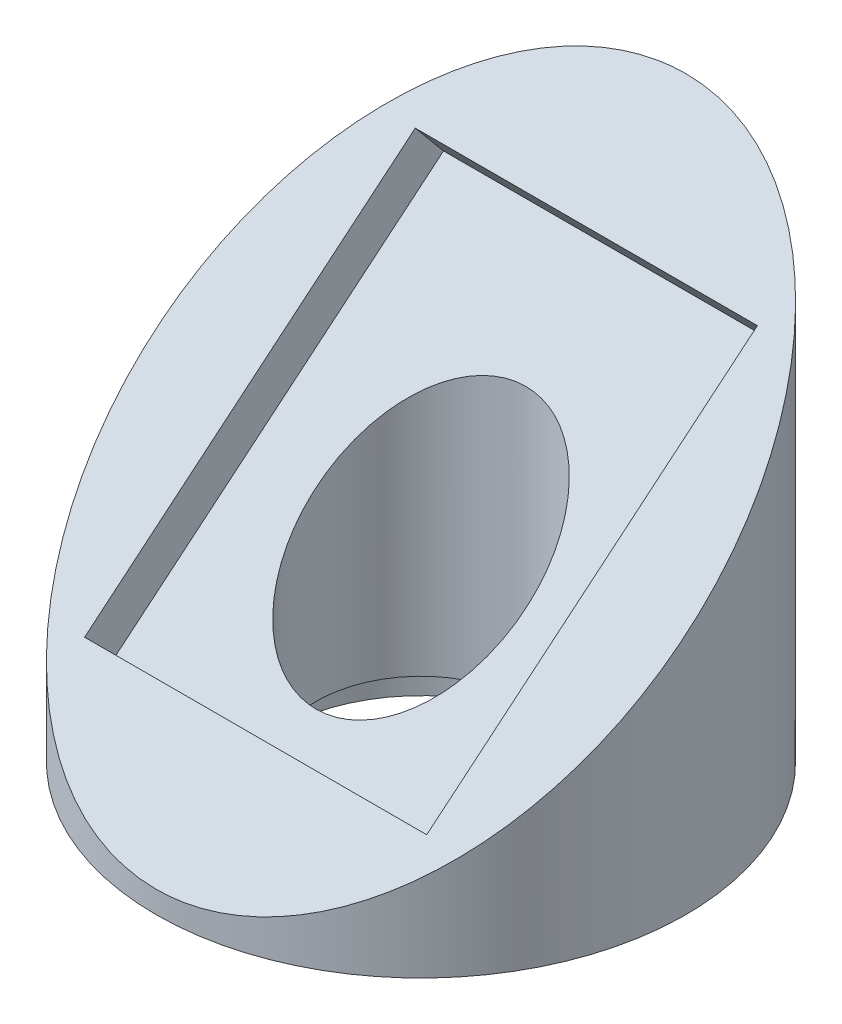
SolidWorks part; units mm, degrees
ref_plane "Front Plane" through (0, 0, 0) normal (0, 0, 1) x (1, 0, 0)
ref_plane "Top Plane" through (0, 0, 0) normal (0, 1, 0) x (1, 0, 0)
ref_plane "Right Plane" through (0, 0, 0) normal (1, 0, 0) x (0, 0, -1)
sketch "Sketch2" plane through (0, 0, 0) normal (0, 1, 0) x (1, 0, 0)
  circle A0 centre (0, 0) radius 4.75
  circle A1 centre (0, 0) radius 6.5
  circle A2 centre (0, 0) radius 12
  circle A3 centre (0, 0) radius 7.5
extrude "Boss-Extrude2" add sketch "Sketch2" against normal blind 1 contours A1 A0 | A3 A1 | A2 A3 region at (-6.3162, 0, 0) region at (-11.6606, 0, 0) region at (-7.2879, 0, 0)
extrude "Boss-Extrude3" add sketch "Sketch2<4>" against normal blind 3 contours A3 A1 region at (-7.2879, 0, 0)
sketch "Sketch2<4>" plane through (0, 0, 0) normal (0, 1, 0) x (1, 0, 0) same geometry as "Sketch2"
extrude "Boss-Extrude4" add sketch "Sketch2<5>" along normal blind 20 contours A0 | A2 region at (0, 0, 0)
sketch "Sketch2<5>" plane through (0, 0, 0) normal (0, 1, 0) x (1, 0, 0) same geometry as "Sketch2"
sketch "Sketch5" plane through (0, 0, 0) normal (1, 0, 0) x (0, 0, -1)
  line L0 (-12, -1) -> (-12, 0)
  line L1 (-12, 20) -> (-12, -1) construction
  line L2 (-12, 0) -> (12, 20)
  line L3 (12, 20) -> (12, -1)
  line L4 (12, -1) -> (-12, -1)
  line L5 (-12, 0) -> (-12, 20)
  line L6 (-12, 20) -> (12, 20)
  line L7 (-12, 20) -> (-12, 0)
extrude "Cut-Extrude1" cut sketch "Sketch5" against normal through all both and the other way through all contours L6 L5 L2 region at (0, 13.3333, 4)
sketch "Sketch10" plane through (0, 5.9016, 4.918) normal (0, 0.7682, 0.6402) x (1, 0, 0)
  line L0 (-12, 6.4018) -> (12, 6.4018)
  line L2 (-7.75, -3.3482) -> (7.75, -3.3482)
  line L3 (-7.75, -3.3482) -> (-7.75, 16.1518)
  line L4 (-7.75, 16.1518) -> (7.75, 16.1518)
  line L5 (7.75, -3.3482) -> (7.75, 16.1518)
  line L6 (-7.75, -3.3482) -> (7.75, 16.1518) construction
  line L7 (-7.75, 16.1518) -> (7.75, -3.3482) construction
  point P4 (0, 6.4018)
  ellipse M4 centre (0, 6.4018) end of major axis (0, 12.585) minor radius 4.75
  dimension "D1" = 15.5
  dimension "D2" = 19.5
extrude "Cut-Extrude5" cut sketch "Sketch10" against normal blind 2 contours L2 L5 L0 L3 M4 | L0 L5 L4 L3 M4 region at (-7.5669, 13.1209, -3.7451) region at (-6.25, 9.8828, 0.1407)
sketch "Sketch11" plane through (0, -2.1434, 2.5721) normal (0, 0.6402, -0.7682) x (-1, 0, 0)
  line L0 (7.75, 5.6822) -> (-7.75, 5.6822) construction
  line L1 (-7.75, 7.6822) -> (7.75, 7.6822)
  line L2 (-7.75, 7.6822) -> (-7.75, 5.6822)
  line L3 (-7.75, 5.6822) -> (7.75, 5.6822)
  line L4 (7.75, 7.6822) -> (7.75, 5.6822)
extrude "Cut-Extrude6" cut sketch "Sketch11" along normal blind 18
thread "Thread2" pitch 1 method extrude profile "Thread Profile2" start angle 0, offset 0, length 0, pitch 1, diameter 15
ref_plane "Plane2" through (7.5, -3, 0) normal (0, 0, 1) x (1, 0, 0)
sketch "Thread Profile2" plane through (7.5, -3, 0) normal (0, 0, 1) x (1, 0, 0)
  line L0 (0, 0) -> (0, 1) construction
  line L1 (0, 0) -> (0.5413, 0.3125)
  line L2 (0.5413, 0.3125) -> (0.5413, 0.4375)
  line L3 (0.5413, 0.4375) -> (0, 0.75)
  line L4 (0.5413, 0.375) -> (0, 0.375) construction
  line L11 (0, 0) -> (0, 0.75)
  point P2 (0, 0)
  dimension "Pitch" = 1
  dimension "Profile_Angle" = 60
  dimension "Profile_Land" = 0.125
  dimension "Profile_Height" = 0.5413
